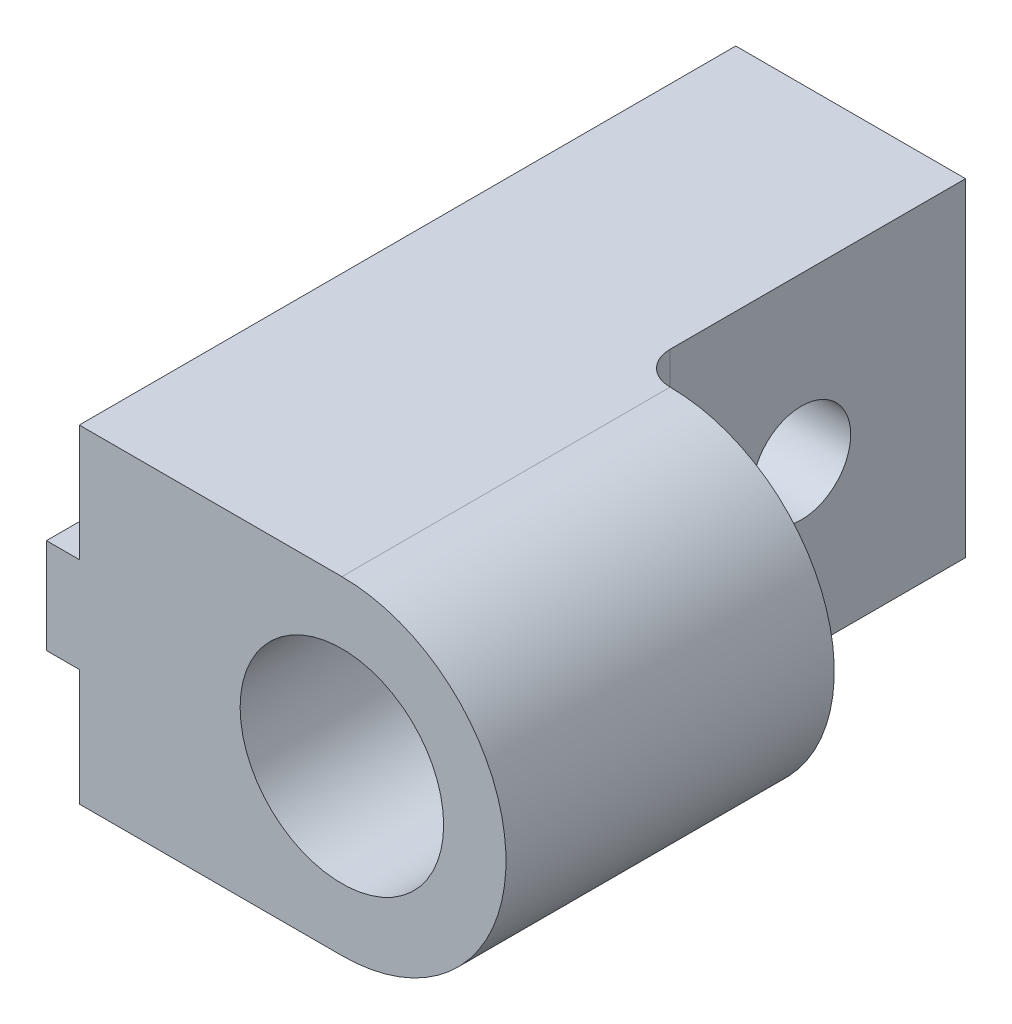
SolidWorks part; units mm, degrees
ref_plane "Front Plane" through (0, 0, 0) normal (0, 0, 1) x (1, 0, 0)
ref_plane "Top Plane" through (0, 0, 0) normal (0, 1, 0) x (1, 0, 0)
ref_plane "Right Plane" through (0, 0, 0) normal (1, 0, 0) x (0, 0, -1)
sketch "Sketch1" plane through (0, 0, 0) normal (0, 0, 1) x (1, 0, 0)
  line L0 (-8, 5) -> (-8, 1.45)
  line L1 (-8, 1.45) -> (-9, 1.45)
  line L2 (-9, 1.45) -> (-9, -1.45)
  line L3 (-9, -1.45) -> (-8, -1.45)
  line L4 (-8, -1.45) -> (-8, -5)
  line L5 (-8, -5) -> (0, -5)
  line L6 (-8, 5) -> (0, 5)
  arc A0 (0, -5) -> (0, 5) centre (0, 0) ccw
  point P9 (-3.4857, 1.45)
  point P10 (-3.5664, -3.6014)
  point P11 (-3.3566, 6.3986)
  point P13 (-8.6216, -3.55)
  point P14 (-7.5557, 0)
  point P15 (1.8113, 1.45)
  point P16 (0, 0)
  dimension "D1" = 10
  dimension "D2" = 2.9
  dimension "D3" = 1
  dimension "D4" = 8
extrude "Main" add sketch "Sketch1" along normal blind 20
ref_plane "Plane1" through (-1, 0, 0) normal (-1, 0, 0) x (0, 0, 1)
sketch "Sketch2" plane through (0, 0, 20) normal (0, 0, 1) x (1, 0, 0)
  circle A0 centre (0, 0) radius 3.1
  dimension "D1" = 6.2
extrude "ShaftHole" cut sketch "Sketch2" against normal blind 5
sketch "Sketch3" plane through (-1, 0, 0) normal (1, 0, 0) x (0, 0, -1)
  line L0 (-20, 5) -> (0, 5) construction
  line L1 (-10, 5) -> (0, 5)
  line L2 (-10, 5) -> (-10, -5)
  line L3 (-10, -5) -> (0, -5)
  line L4 (0, 5) -> (0, -5)
  line L5 (-20, -5) -> (0, -5) construction
  line L6 (0, -5) -> (0, 5) construction
  point P4 (-10.6427, 5)
  point P7 (-0.1223, 5)
  point P8 (-10.6427, -5)
  point P11 (0, -5)
  dimension "D1" = 10
extrude "MakerBeamRectangularHole" cut sketch "Sketch3" along normal through all
sketch "Sketch4" plane through (-1, 0, 0) normal (1, 0, 0) x (0, 0, -1)
  line L0 (0, -5) -> (0, 5) construction
  circle A0 centre (-5, 0) radius 1.5
  point P2 (0, 0)
  dimension "D1" = 3
  dimension "D2" = 5
extrude "MakerBeamHole" cut sketch "Sketch4" against normal through all
fillet "Fillet1" radius 1 1 edges at (-1, 0, 10)
